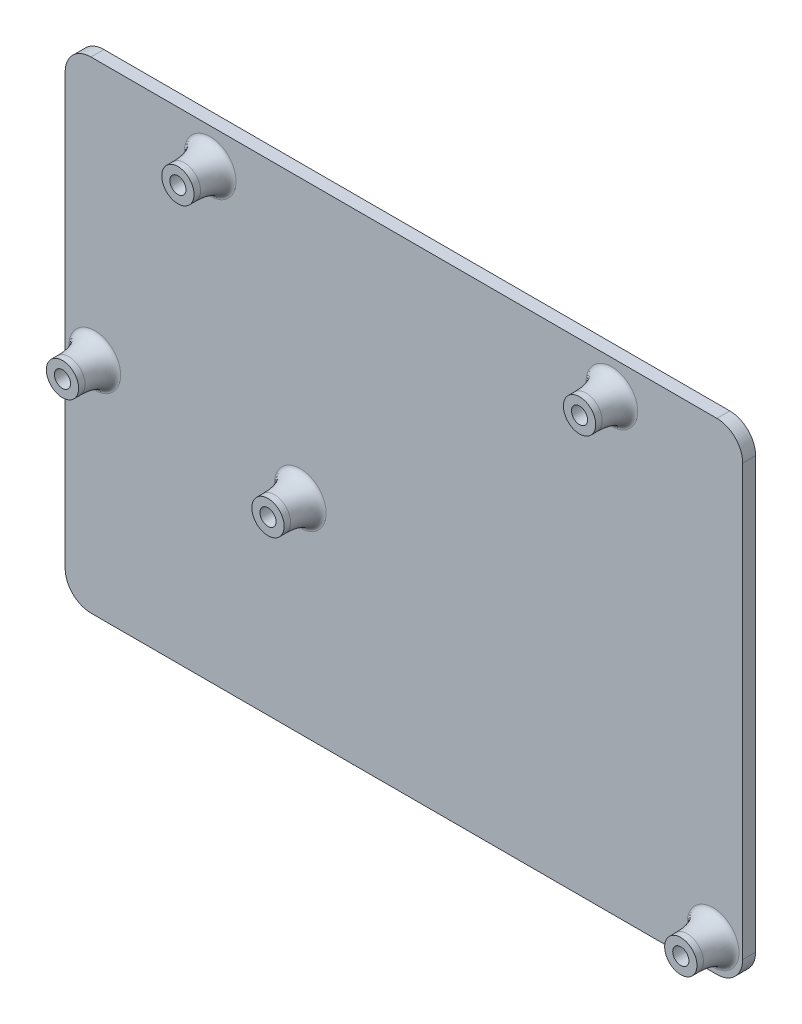
SolidWorks part; units mm, degrees
ref_plane "Front Plane" through (0, 0, 0) normal (0, 0, 1) x (1, 0, 0)
ref_plane "Top Plane" through (0, 0, 0) normal (0, 1, 0) x (1, 0, 0)
ref_plane "Right Plane" through (0, 0, 0) normal (1, 0, 0) x (0, 0, -1)
sketch "Sketch1" plane through (0, 0, 0) normal (0, 0, 1) x (1, 0, 0)
  line L1 (-49.6429, 25.8106) -> (51.2071, 25.8106)
  line L2 (-49.6429, 25.8106) -> (-49.6429, -44.7194)
  line L3 (-49.6429, -44.7194) -> (51.2071, -44.7194)
  line L4 (51.2071, 25.8106) -> (51.2071, -44.7194)
  dimension "D1" = 100.85
  dimension "D2" = 70.53
extrude "Boss-Extrude1" add sketch "Sketch1" along normal blind 2
sketch "Sketch2" plane through (0, 0, 2) normal (0, 0, 1) x (1, 0, 0)
  line L0 (-49.6429, 25.8106) -> (-49.6429, -44.7194) construction
  line L2 (-49.6429, -44.7194) -> (51.2071, -44.7194) construction
  point P0 (-29.1929, 22.3606)
  point P1 (-47.0529, -12.5594)
  point P2 (-15.2529, -15.1494)
  point P3 (48.6271, -42.0494)
  point P4 (32.9571, 22.5906)
  dimension "D1" = 20.45
  dimension "D2" = 67.08
  dimension "D3" = 67.31
  dimension "D4" = 82.6
  dimension "D5" = 2.59
  dimension "D6" = 32.16
  dimension "D7" = 34.39
  dimension "D8" = 29.57
  dimension "D9" = 2.67
  dimension "D10" = 98.27
sketch "Sketch6" plane through (0, 0, 2) normal (0, 0, 1) x (1, 0, 0)
  line L8 (-51.6429, 27.8106) -> (-51.6429, -46.7194)
  line L9 (-51.6429, -46.7194) -> (53.2071, -46.7194)
  line L10 (53.2071, -46.7194) -> (53.2071, 27.8106)
  line L11 (53.2071, 27.8106) -> (-51.6429, 27.8106)
  line L12 (-51.6429, 27.8106) -> (-51.6429, -46.7194)
  line L13 (-51.6429, -46.7194) -> (53.2071, -46.7194)
  line L14 (53.2071, -46.7194) -> (53.2071, 27.8106)
  line L16 (53.2071, 27.8106) -> (-51.6429, 27.8106)
  dimension "D1" = 2
extrude "Boss-Extrude3" add sketch "Sketch6" against normal up to surface (2 mm away) up to face at (0.7821, -9.4544, 0)
sketch "Sketch3" plane through (0, 0, 2) normal (0, 0, 1) x (1, 0, 0)
  circle A0 centre (-29.1929, 22.3606) radius 2.5
  dimension "D1" = 5
extrude "Boss-Extrude2" add sketch "Sketch3" along normal blind 5
hole_wizard "Tap Drill for M3x0.5 Tap1" positions "Sketch4" profile "Sketch5" hole size "M3x0.5" standard "ANSI Metric"
sketch "Sketch4" plane through (0, 0, 7) normal (0, 0, 1) x (1, 0, 0)
  point P0 (-29.1929, 22.3606)
sketch "Sketch5" plane through (-29.1929, 22.3606, 7) normal (1, 0, 0) x (0, -1, 0)
  line L0 (0, 0) -> (0, 10.7511)
  line L1 (0, 10.7511) -> (1.25, 10)
  line L2 (1.25, 10) -> (1.25, 0)
  line L5 (1.25, 0) -> (0, 0)
  line L10 (0, 10.7511) -> (-1.25, 10) construction
  line L11 (0, -6.35) -> (0, 107.95) construction
  dimension "Hole Dia." = 2.5
  dimension "Hole Depth" = 10
  dimension "Drill Angle" = 118
pattern_sketch "Sketch-Pattern1" of "Boss-Extrude2", "Tap Drill for M3x0.5 Tap1" driven by "Sketch2"
fillet "Fillet1" radius 1.5 1 edges at (-26.6929, 22.3606, 2)
fillet "Fillet2" radius 4 4 edges at (-51.6429, 27.8106, 1) (53.2071, 27.8106, 1) (53.2071, -46.7194, 1) (-51.6429, -46.7194, 1)
